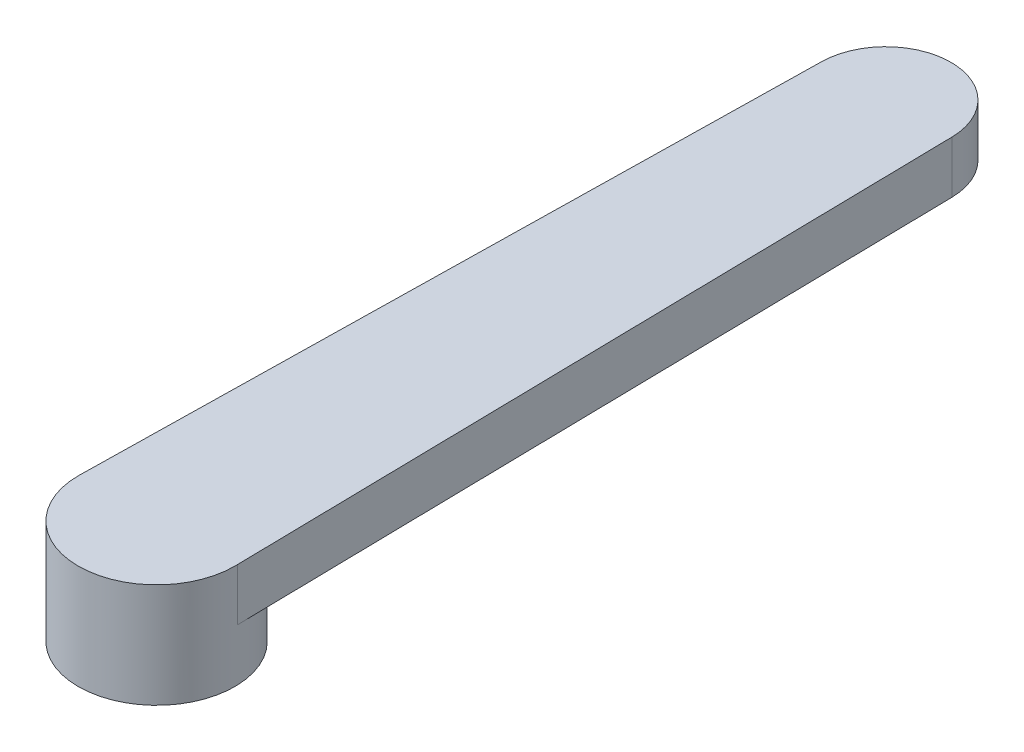
SolidWorks part; units mm, degrees
material "ABS PC"
ref_plane "Front Plane" through (0, 0, 0) normal (0, 0, 1) x (1, 0, 0)
ref_plane "Top Plane" through (0, 0, 0) normal (0, 1, 0) x (1, 0, 0)
ref_plane "Right Plane" through (0, 0, 0) normal (1, 0, 0) x (0, 0, -1)
sketch "Sketch1" plane through (0, 0, 0) normal (0, 1, 0) x (1, 0, 0)
  circle A0 centre (0, 0) radius 2.35
  circle A1 centre (0, 0) radius 3
  dimension "D1" = 4.7
  dimension "D2" = 6
extrude "Boss-Extrude1" add sketch "Sketch1" along normal blind 4
sketch "Sketch2" plane through (0, 4, 0) normal (0, 1, 0) x (1, 0, 0)
  circle A0 centre (0, 0) radius 3
extrude "Boss-Extrude2" add sketch "Sketch2" against normal blind 1
sketch "Sketch3" plane through (0, 4, 0) normal (0, 1, 0) x (1, 0, 0)
  line L2 (-3, 0) -> (-2.5, 27.9955)
  line L4 (3, 0) -> (2.4992, 27.9956)
  line L5 (3, 0) -> (2.35, 0)
  line L6 (-2.35, 0) -> (-3, 0)
  circle A0 centre (0, 0) radius 3 construction
  arc A1 (-2.5, 27.9955) -> (2.4992, 27.9956) centre (-0.0004, 27.9509) cw
  arc A3 (2.35, 0) -> (-2.35, 0) centre (0, 0) ccw
  circle A4 centre (0, 0) radius 2.35 construction
  point P0 (0, 0)
  dimension "D2" = 27.9955
  dimension "D4" = 2.048
  dimension "D1" = 2.5
  dimension "D7" = 2.35
  dimension "D3" = 6
  dimension "D6" = 27.9956
extrude "Boss-Extrude4" add sketch "Sketch3" against normal blind 2
